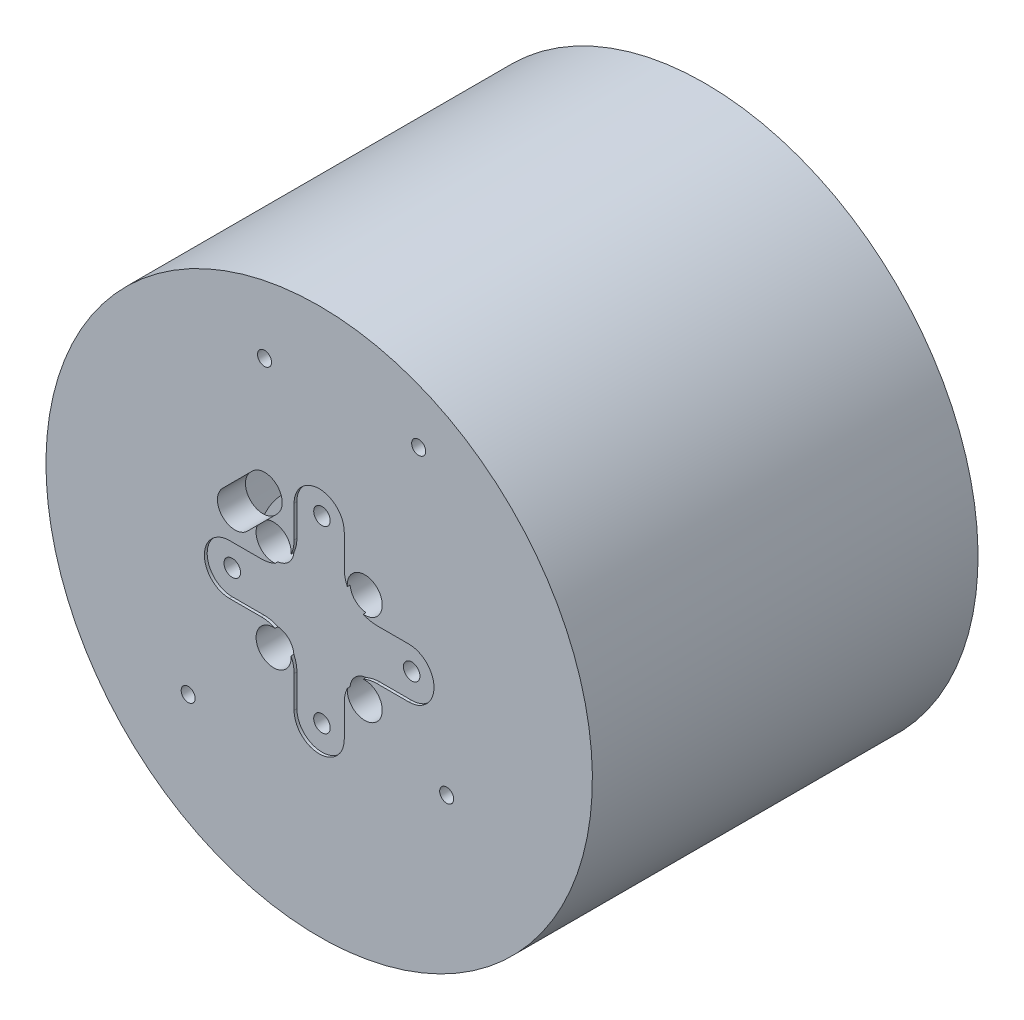
SolidWorks part; units mm, degrees
note: The reader was unsure of these and kept them because the rebuilt part matched: shared geometry of "Sketch4<3>", "Sketch6<4>", "Sketch6<3>", "Sketch4<5>".
ref_plane "Front Plane" through (0, 0, 0) normal (0, 0, 1) x (1, 0, 0)
ref_plane "Top Plane" through (0, 0, 0) normal (0, 1, 0) x (1, 0, 0)
ref_plane "Right Plane" through (0, 0, 0) normal (1, 0, 0) x (0, 0, -1)
sketch "Sketch2" plane through (0, 0, 0) normal (1, 0, 0) x (0, 0, -1)
  line L0 (0, 12.5857) -> (0, 0)
  line L1 (0, -12.5857) -> (4.4704, -13.9065)
  line L2 (4.4704, 13.9065) -> (4.4704, 16.4465)
  line L3 (4.4704, 16.4465) -> (0, 16.4465)
  line L4 (0, 16.4465) -> (0, 44.45)
  line L5 (0, 44.45) -> (59.7512, 44.45)
  line L6 (59.7512, 44.45) -> (59.7512, 39.37)
  line L7 (59.7512, 39.37) -> (64.8312, 39.37)
  line L8 (64.8312, 39.37) -> (64.8312, 49.53)
  line L9 (64.8312, 49.53) -> (-5.08, 49.53)
  line L10 (-5.08, 49.53) -> (-5.08, 0)
  line L12 (0, 0) -> (-5.08, 0)
  line L17 (0, 12.0425) -> (0, 12.5857) construction
  line L19 (4.4704, 13.9065) -> (0, 12.5857)
  line L20 (4.4704, 13.9065) -> (0, 12.5857)
  line L21 (0, -12.5857) -> (4.4704, -13.9065)
  dimension "D1" = 2.54
  dimension "D2" = 5.08
  dimension "D3" = 44.45
  dimension "D4" = 5.08
  dimension "D5" = 5.08
  dimension "D6" = 5.08
revolve "Body" add sketch "Sketch2" angle 360 about L12
sketch "Sketch4" plane through (0, 0, 0) normal (0, 0, 1) x (1, 0, 0)
  line L0 (-3.6576, 12.0425) -> (-3.6576, 10.4835)
  line L1 (-3.6576, 16.265) -> (-3.6576, 12.0425)
  line L2 (-3.6576, 16.265) -> (-3.6576, 12.0425) construction
  line L3 (-3.6576, 12.0425) -> (-3.6576, 10.4835) construction
  line L4 (3.6576, 12.0425) -> (3.6576, 10.4835)
  line L5 (3.6576, 16.265) -> (3.6576, 12.0425)
  line L6 (3.6576, 16.265) -> (3.6576, 12.0425) construction
  line L7 (3.6576, 12.0425) -> (3.6576, 10.4835) construction
  line L8 (12.0425, 3.6576) -> (10.4835, 3.6576)
  line L9 (16.265, 3.6576) -> (12.0425, 3.6576)
  line L10 (16.265, 3.6576) -> (12.0425, 3.6576) construction
  line L11 (12.0425, 3.6576) -> (10.4835, 3.6576) construction
  line L12 (12.0425, -3.6576) -> (10.4835, -3.6576)
  line L13 (16.265, -3.6576) -> (12.0425, -3.6576)
  line L14 (16.265, -3.6576) -> (12.0425, -3.6576) construction
  line L15 (12.0425, -3.6576) -> (10.4835, -3.6576) construction
  line L16 (3.6576, -12.0425) -> (3.6576, -10.4835)
  line L17 (3.6576, -16.265) -> (3.6576, -12.0425)
  line L18 (3.6576, -16.265) -> (3.6576, -12.0425) construction
  line L19 (3.6576, -12.0425) -> (3.6576, -10.4835) construction
  line L20 (-3.6576, -12.0425) -> (-3.6576, -10.4835)
  line L21 (-3.6576, -16.265) -> (-3.6576, -12.0425)
  line L22 (-3.6576, -16.265) -> (-3.6576, -12.0425) construction
  line L23 (-3.6576, -12.0425) -> (-3.6576, -10.4835) construction
  line L24 (-12.0425, 3.6576) -> (-10.4835, 3.6576)
  line L25 (-16.265, 3.6576) -> (-12.0425, 3.6576)
  line L26 (-16.265, 3.6576) -> (-12.0425, 3.6576) construction
  line L27 (-12.0425, 3.6576) -> (-10.4835, 3.6576) construction
  line L28 (-4.1656, -12.0425) -> (-4.1656, -10.4835)
  line L29 (-4.1656, -16.265) -> (-4.1656, -12.0425)
  line L30 (4.1656, -16.265) -> (4.1656, -12.0425)
  line L31 (4.1656, -12.0425) -> (4.1656, -10.4835)
  line L32 (12.0425, -4.1656) -> (10.4835, -4.1656)
  line L33 (16.265, -4.1656) -> (12.0425, -4.1656)
  line L34 (16.265, 4.1656) -> (12.0425, 4.1656)
  line L35 (12.0425, 4.1656) -> (10.4835, 4.1656)
  line L36 (4.1656, 12.0425) -> (4.1656, 10.4835)
  line L37 (4.1656, 16.265) -> (4.1656, 12.0425)
  line L38 (-4.1656, 16.265) -> (-4.1656, 12.0425)
  line L39 (-4.1656, 12.0425) -> (-4.1656, 10.4835)
  line L40 (-12.0425, 4.1656) -> (-10.4835, 4.1656)
  line L41 (-16.265, 4.1656) -> (-12.0425, 4.1656)
  line L42 (-10.4835, -4.1656) -> (-16.265, -4.1656)
  line L43 (-9.8783, 15.2664) -> (-15.2664, 9.8783) construction
  line L44 (-7.6332, 13.0214) -> (-13.0214, 7.6332)
  line L45 (-12.1233, 17.5115) -> (-17.5115, 12.1233)
  line L46 (0, 0) -> (-26.7135, 26.7135) construction
  line L47 (0, 0) -> (0, 36.3192) construction
  line L48 (-8.2611, -8.2611) -> (8.2611, 8.2611) construction
  line L49 (0, 0) -> (8.2611, -8.2611) construction
  line L50 (-10.4835, -4.5466) -> (-16.265, -4.5466)
  line L51 (-16.265, 4.5466) -> (-12.0425, 4.5466)
  line L52 (-12.0425, 4.5466) -> (-10.4835, 4.5466)
  line L53 (-4.5466, 12.0425) -> (-4.5466, 10.4835)
  line L54 (-4.5466, 16.265) -> (-4.5466, 12.0425)
  line L55 (4.5466, 16.265) -> (4.5466, 12.0425)
  line L56 (4.5466, 12.0425) -> (4.5466, 10.4835)
  line L57 (12.0425, 4.5466) -> (10.4835, 4.5466)
  line L58 (16.265, 4.5466) -> (12.0425, 4.5466)
  line L59 (16.265, -4.5466) -> (12.0425, -4.5466)
  line L60 (12.0425, -4.5466) -> (10.4835, -4.5466)
  line L61 (4.5466, -12.0425) -> (4.5466, -10.4835)
  line L62 (4.5466, -16.265) -> (4.5466, -12.0425)
  line L63 (-4.5466, -16.265) -> (-4.5466, -12.0425)
  line L64 (-4.5466, -12.0425) -> (-4.5466, -10.4835)
  arc A0 (-10.4835, 3.6576) -> (-3.6576, 10.4835) centre (-10.4835, 10.4835) ccw
  arc A1 (-10.4835, 3.6576) -> (-3.6576, 10.4835) centre (-10.4835, 10.4835) ccw construction
  arc A2 (3.6576, 16.265) -> (-3.6576, 16.265) centre (0, 16.265) ccw
  arc A3 (3.6576, 16.265) -> (-3.6576, 16.265) centre (0, 16.265) ccw construction
  arc A4 (3.6576, 10.4835) -> (10.4835, 3.6576) centre (10.4835, 10.4835) ccw
  arc A5 (3.6576, 10.4835) -> (10.4835, 3.6576) centre (10.4835, 10.4835) ccw construction
  arc A6 (16.265, -3.6576) -> (16.265, 3.6576) centre (16.265, 0) ccw
  arc A7 (16.265, -3.6576) -> (16.265, 3.6576) centre (16.265, 0) ccw construction
  arc A8 (10.4835, -3.6576) -> (3.6576, -10.4835) centre (10.4835, -10.4835) ccw
  arc A9 (10.4835, -3.6576) -> (3.6576, -10.4835) centre (10.4835, -10.4835) ccw construction
  arc A10 (-3.6576, -16.265) -> (3.6576, -16.265) centre (0, -16.265) ccw
  arc A11 (-3.6576, -16.265) -> (3.6576, -16.265) centre (0, -16.265) ccw construction
  arc A12 (-3.6576, -10.4835) -> (-10.4835, -3.6576) centre (-10.4835, -10.4835) ccw
  arc A13 (-3.6576, -10.4835) -> (-10.4835, -3.6576) centre (-10.4835, -10.4835) ccw construction
  arc A14 (-16.265, 3.6576) -> (-16.265, -3.6576) centre (-16.265, 0) ccw
  arc A15 (-16.265, 3.6576) -> (-16.265, -3.6576) centre (-16.265, 0) ccw construction
  arc A16 (-4.1656, -10.4835) -> (-10.4835, -4.1656) centre (-10.4835, -10.4835) ccw
  arc A17 (-4.1656, -16.265) -> (4.1656, -16.265) centre (0, -16.265) ccw
  arc A18 (10.4835, -4.1656) -> (4.1656, -10.4835) centre (10.4835, -10.4835) ccw
  arc A19 (16.265, -4.1656) -> (16.265, 4.1656) centre (16.265, 0) ccw
  arc A20 (4.1656, 10.4835) -> (10.4835, 4.1656) centre (10.4835, 10.4835) ccw
  arc A21 (4.1656, 16.265) -> (-4.1656, 16.265) centre (0, 16.265) ccw
  arc A22 (-10.4835, 4.1656) -> (-4.1656, 10.4835) centre (-10.4835, 10.4835) ccw
  arc A23 (-16.265, 4.1656) -> (-16.265, -4.1656) centre (-16.265, 0) ccw
  circle A24 centre (16.265, 0) radius 1.5
  circle A25 centre (0, 16.265) radius 1.5
  circle A26 centre (-16.265, 0) radius 1.5
  circle A27 centre (0, -16.265) radius 1.5
  arc A28 (-7.6332, 13.0214) -> (-12.1233, 17.5115) centre (-9.8783, 15.2664) ccw
  arc A29 (-17.5115, 12.1233) -> (-13.0214, 7.6332) centre (-15.2664, 9.8783) ccw
  circle A30 centre (8.2611, 8.2611) radius 3.175
  circle A31 centre (8.2611, -8.2611) radius 3.175
  circle A32 centre (-8.2611, -8.2611) radius 3.175
  circle A33 centre (-8.2611, 8.2611) radius 3.175
  arc A34 (-16.265, 4.5466) -> (-16.265, -4.5466) centre (-16.265, 0) ccw
  arc A35 (-10.4835, 4.5466) -> (-4.5466, 10.4835) centre (-10.4835, 10.4835) ccw
  arc A36 (4.5466, 16.265) -> (-4.5466, 16.265) centre (0, 16.265) ccw
  arc A37 (4.5466, 10.4835) -> (10.4835, 4.5466) centre (10.4835, 10.4835) ccw
  arc A38 (16.265, -4.5466) -> (16.265, 4.5466) centre (16.265, 0) ccw
  arc A39 (10.4835, -4.5466) -> (4.5466, -10.4835) centre (10.4835, -10.4835) ccw
  arc A40 (-4.5466, -16.265) -> (4.5466, -16.265) centre (0, -16.265) ccw
  arc A41 (-4.5466, -10.4835) -> (-10.4835, -4.5466) centre (-10.4835, -10.4835) ccw
  point P68 (-12.5724, 12.5724)
  dimension "D2" = 3
  dimension "D7" = 6.35
  dimension "D3" = 45
  dimension "D4" = 17.78
  dimension "D5" = 6.35
  dimension "D6" = 7.62
  dimension "D1" = 0.508
  dimension "D8" = 0.381
extrude "X-Wing" cut sketch "Sketch4" against normal blind 12.7 contours A17 L30 L31 A18 L32 L33 A19 L34 L35 A20 L36 L37 A21 L38 L39 A22 L40 L41 A23 L42 A16 L28 L29
extrude "Holes" cut sketch "Sketch4<3>" along normal blind 9.525 contours A27 | A26 | A24 | A25 | A28 L45 A29 L44 | A33 | A30 | A31 | A32
sketch "Sketch4<3>" plane through (0, 0, 0) normal (0, 0, 1) x (1, 0, 0) same geometry as "Sketch4"
sketch "Sketch6" plane through (0, 0, 5.08) normal (0, 0, 1) x (1, 0, 0)
  line L0 (-14.605, 22.225) -> (14.605, 22.225)
  line L1 (-12.954, 28.067) -> (12.954, 28.067)
  line L2 (-12.954, 28.067) -> (-12.954, -22.733)
  line L3 (-12.954, -22.733) -> (12.954, -22.733)
  line L4 (12.954, 28.067) -> (12.954, -22.733)
  line L5 (-12.954, 28.067) -> (12.954, -22.733) construction
  line L6 (-12.954, -22.733) -> (12.954, 28.067) construction
  line L7 (-12.7, 20.32) -> (12.7, 20.32)
  line L8 (-12.7, 20.32) -> (-12.7, -20.32)
  line L9 (-12.7, -20.32) -> (12.7, -20.32)
  line L10 (12.7, 20.32) -> (12.7, -20.32)
  line L11 (-12.7, 20.32) -> (12.7, -20.32) construction
  line L12 (-12.7, -20.32) -> (12.7, 20.32) construction
  line L13 (14.605, 22.225) -> (14.605, -22.225)
  line L14 (-14.605, -22.225) -> (14.605, -22.225)
  line L15 (-14.605, 22.225) -> (-14.605, -22.225)
  line L16 (-14.859, 29.972) -> (-14.859, -24.638)
  line L17 (-14.859, -24.638) -> (14.859, -24.638)
  line L18 (14.859, 29.972) -> (14.859, -24.638)
  line L19 (-14.859, 29.972) -> (14.859, 29.972)
  line L20 (-14.859, 23.4798) -> (-11.7157, 23.4798)
  line L21 (-12.954, 28.067) -> (-14.859, 28.067)
  line L22 (-11.7157, 23.4798) -> (-11.7157, 22.225)
  line L23 (-12.954, -22.733) -> (12.954, -22.733)
  line L24 (-12.954, -22.733) -> (-12.954, 22.733)
  line L25 (-12.954, 22.733) -> (12.954, 22.733) construction
  line L26 (12.954, -22.733) -> (12.954, 22.733)
  line L27 (-12.954, -22.733) -> (12.954, 22.733) construction
  line L28 (-12.954, 22.733) -> (12.954, -22.733) construction
  line L30 (12.954, 23.7342) -> (11.35, 23.7342)
  line L31 (12.954, 23.7342) -> (12.954, 22.225)
  line L32 (12.954, 22.225) -> (11.35, 22.225)
  line L33 (11.35, 23.7342) -> (11.35, 22.225)
  line L34 (12.954, 23.7342) -> (11.35, 22.225) construction
  line L35 (12.954, 22.225) -> (11.35, 23.7342) construction
  circle A0 centre (-9.906, 36.322) radius 1.27
  circle A1 centre (-23.749, -23.368) radius 1.27
  circle A2 centre (23.114, -15.748) radius 1.27
  circle A3 centre (18.034, 36.322) radius 1.27
  circle A4 centre (18.034, 36.322) radius 1.5875 construction
  circle A5 centre (-9.906, 36.322) radius 1.5875 construction
  circle A6 centre (-23.749, -23.368) radius 1.5 construction
  circle A7 centre (23.114, -15.748) radius 1.5875 construction
  point P4 (0, 0)
  point P9 (0, 0)
  point P12 (0, 2.667)
  point P41 (0, 0)
  point P48 (12.152, 22.9796)
  circle M35 centre (16.265, 0) radius 1.5
  circle M36 centre (-16.265, 0) radius 1.5
  arc M45 (-13.0214, 7.6332) -> (-17.5115, 12.1233) centre (-15.2664, 9.8783) cw
  line M46 (-17.5115, 12.1233) -> (-12.1233, 17.5115)
  line M49 (-11.2055, 9.4491) -> (-13.0214, 7.6332)
  dimension "D9" = 2.54
  dimension "D1" = 25.908
  dimension "D2" = 50.8
  dimension "D3" = 45.466
  dimension "D5" = 40.64
  dimension "D6" = 25.4
  dimension "D10" = 1.905
extrude "Chip" add sketch "Sketch6" along normal blind 6.35 contours L2 L14 L4 L0 L8 L7 L10 L9 M46 M49 M45 | L16 L17 L18 L19
extrude "9V" add sketch "Sketch6<4>" along normal blind 15.24 contours L19 L16 L15 L0 L2 L1 L4 L13 L14 L3 L17 L18 M46 M45 M36 M35 | L15 L14 L2 M45 | L4 L14 L13 L0 | L0 L15 L2 M46 | L20 L16 L15 L0 L2 M46 | L22 L20 L2 L0 | L30 L33 L32 L31
sketch "Sketch6<4>" plane through (0, 0, 5.08) normal (0, 0, 1) x (1, 0, 0) same geometry as "Sketch6"
extrude "Air holes" cut sketch "Sketch6<3>" against normal blind 9.525 contours A1 | A2 | A0 | A3
sketch "Sketch6<3>" plane through (0, 0, 5.08) normal (0, 0, 1) x (1, 0, 0) same geometry as "Sketch6"
sketch "Sketch7" plane through (0, 0, 5.08) normal (0, 0, 1) x (1, 0, 0)
  line L1 (11.766, 12.6721) -> (19.309, 12.6721)
  line L2 (11.766, 12.6721) -> (11.766, 4.7914)
  line L3 (11.766, 4.7914) -> (19.309, 4.7914)
  line L4 (19.309, 12.6721) -> (19.309, 4.7914)
  line L5 (11.766, 12.6721) -> (19.309, 4.7914) construction
  line L6 (11.766, 4.7914) -> (19.309, 12.6721) construction
  line L7 (11.766, -5.1158) -> (19.309, -5.1158)
  line L8 (11.766, -5.1158) -> (11.766, -11.5329)
  line L9 (11.766, -11.5329) -> (19.309, -11.5329)
  line L10 (19.309, -5.1158) -> (19.309, -11.5329)
  line L11 (11.766, -5.1158) -> (19.309, -11.5329) construction
  line L12 (11.766, -11.5329) -> (19.309, -5.1158) construction
  line L13 (-17.7303, -5.1158) -> (-11.9886, -5.1158)
  line L14 (-17.7303, -5.1158) -> (-17.7303, -13.3342)
  line L15 (-17.7303, -13.3342) -> (-11.9886, -13.3342)
  line L16 (-11.9886, -5.1158) -> (-11.9886, -13.3342)
  line L17 (-17.7303, -5.1158) -> (-11.9886, -13.3342) construction
  line L18 (-17.7303, -13.3342) -> (-11.9886, -5.1158) construction
  point P4 (15.5375, 8.7317)
  point P9 (15.5375, -8.3243)
  point P14 (-14.8595, -9.225)
extrude "Air Slots" cut sketch "Sketch7" along normal blind 1.27
sketch "Sketch8" plane through (0, 0, 5.08) normal (0, 0, 1) x (1, 0, 0)
  line L0 (0, 0) -> (0, 28.448) construction
  line L1 (-11.684, -22.352) -> (11.684, -22.352)
  line L2 (-12.954, -21.082) -> (-12.954, 21.082)
  line L3 (-11.684, 22.352) -> (-10.795, 22.352)
  line L4 (12.954, -21.082) -> (12.954, 21.082)
  line L5 (-12.954, -22.352) -> (12.954, 22.352) construction
  line L6 (-12.954, 22.352) -> (12.954, -22.352) construction
  line L7 (-15.494, -21.082) -> (-15.494, -4.7901)
  line L8 (-9.525, 28.448) -> (9.525, 28.448)
  line L9 (-13.335, 24.5157) -> (-13.335, 27.178)
  line L10 (-10.795, 22.352) -> (-10.795, 27.178)
  line L11 (10.795, 22.352) -> (11.684, 22.352)
  line L12 (10.795, 22.352) -> (10.795, 27.178)
  line L13 (-9.525, 30.988) -> (9.525, 30.988)
  line L14 (13.335, 24.5157) -> (13.335, 27.178)
  line L15 (15.494, -21.082) -> (15.494, 21.082)
  line L16 (-11.684, -24.892) -> (11.684, -24.892)
  line L17 (-15.494, -2.8851) -> (-15.494, 21.082)
  line L18 (-28.194, -2.8851) -> (-15.494, -2.8851)
  line L19 (-28.194, -2.8851) -> (-28.194, -4.7901)
  line L20 (-28.194, -4.7901) -> (-15.494, -4.7901)
  line L21 (-13.335, 27.178) -> (-10.795, 27.178)
  line L22 (-13.335, 24.5157) -> (-10.795, 24.5157)
  circle A0 centre (0, 1.27) radius 28.8925 construction
  arc A1 (-11.684, 22.352) -> (-12.954, 21.082) centre (-11.684, 21.082) ccw
  arc A2 (-9.525, 28.448) -> (-10.795, 27.178) centre (-9.525, 27.178) ccw
  arc A3 (9.525, 28.448) -> (10.795, 27.178) centre (9.525, 27.178) cw
  arc A4 (11.684, 22.352) -> (12.954, 21.082) centre (11.684, 21.082) cw
  arc A5 (12.954, -21.082) -> (11.684, -22.352) centre (11.684, -21.082) cw
  arc A6 (-11.684, -22.352) -> (-12.954, -21.082) centre (-11.684, -21.082) cw
  arc A7 (-13.335, 24.5157) -> (-15.494, 21.082) centre (-11.684, 21.082) ccw
  arc A8 (-9.525, 30.988) -> (-13.335, 27.178) centre (-9.525, 27.178) ccw
  arc A9 (9.525, 30.988) -> (13.335, 27.178) centre (9.525, 27.178) cw
  arc A10 (13.335, 24.5157) -> (15.494, 21.082) centre (11.684, 21.082) cw
  arc A11 (15.494, -21.082) -> (11.684, -24.892) centre (11.684, -21.082) cw
  arc A12 (-11.684, -24.892) -> (-15.494, -21.082) centre (-11.684, -21.082) cw
  point P0 (0, 0)
  dimension "D5" = 1.27
  dimension "D1" = 44.704
  dimension "D2" = 25.908
  dimension "D3" = 50.8
  dimension "D4" = 1.27
  dimension "D6" = 12.7
  dimension "D7" = 1.905
ref_plane "Plane1" through (0, 0, 5.08) normal (0, 0, 1) x (1, 0, 0)
other "SurfaceCut1"
extrude "Cut-Extrude1" cut sketch "Sketch4<5>" against normal blind 0.508 from vertex contours A36 L54 L53 A35 L52 L51 A34 L50 A41 L64 L63 A40 L62 L61 A39 L60 L59 A38 L58 L57 A37 L56 L55
sketch "Sketch4<5>" plane through (0, 0, 0) normal (0, 0, 1) x (1, 0, 0) same geometry as "Sketch4"
